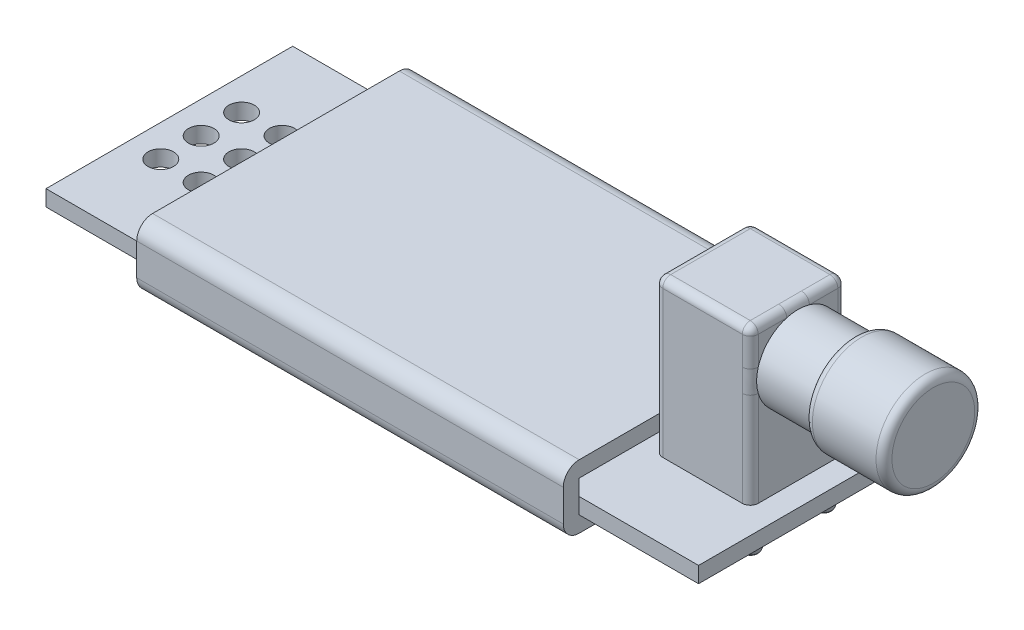
SolidWorks part; units mm, degrees
ref_plane "Спереди" through (0, 0, 0) normal (0, 0, 1) x (1, 0, 0)
ref_plane "Сверху" through (0, 0, 0) normal (0, 1, 0) x (1, 0, 0)
ref_plane "Справа" through (0, 0, 0) normal (1, 0, 0) x (0, 0, -1)
sketch "Эскиз1" plane through (0, 0, 0) normal (0, 1, 0) x (1, 0, 0)
  line L1 (-20.5, 7.75) -> (20.5, 7.75)
  line L2 (-20.5, 7.75) -> (-20.5, -7.75)
  line L3 (-20.5, -7.75) -> (20.5, -7.75)
  line L4 (20.5, 7.75) -> (20.5, -7.75)
  line L5 (-20.5, 7.75) -> (20.5, -7.75) construction
  line L6 (-20.5, -7.75) -> (20.5, 7.75) construction
  point P0 (0, 0)
  dimension "D1" = 15.5
  dimension "D2" = 41
extrude "Бобышка-Вытянуть1" add sketch "Эскиз1" along normal blind 1
sketch "Эскиз2" plane through (0, 1, 0) normal (0, 1, 0) x (1, 0, 0)
  line L1 (13, 3) -> (19, 3)
  line L2 (13, 3) -> (13, -3)
  line L3 (13, -3) -> (19, -3)
  line L4 (19, 3) -> (19, -3)
  line L5 (20.5, -7.75) -> (20.5, 7.75) construction
  point P4 (13, 0)
  dimension "D1" = 6
  dimension "D2" = 1.5
extrude "Бобышка-Вытянуть2" add sketch "Эскиз2" along normal blind 9.7
sketch "Эскиз3" plane through (19, 0, 0) normal (1, 0, 0) x (0, 0, -1)
  line L0 (-3, 10.7) -> (3, 10.7) construction
  line L1 (0, 10.7) -> (0, 7.7) construction
  line L2 (0, 7.7) -> (-3, 7.7) construction
  line L3 (-3, 10.7) -> (-3, 1) construction
  circle A0 centre (0, 7.7) radius 2.6
  point P5 (0, 10.7)
  dimension "D1" = 5.2
extrude "Бобышка-Вытянуть3" add sketch "Эскиз3" along normal blind 3.5
sketch "Эскиз4" plane through (0, 1, 0) normal (0, 1, 0) x (1, 0, 0)
  line L0 (-20.5, 7.75) -> (-20.5, -7.75) construction
  circle A0 centre (-18.5, -2.54) radius 0.8
  circle A1 centre (-15.96, -2.54) radius 0.8
  circle A2 centre (-15.96, 0) radius 0.8
  circle A3 centre (-15.96, 2.54) radius 0.8
  circle A4 centre (-18.5, 0) radius 0.8
  circle A5 centre (-18.5, 2.54) radius 0.8
  point P16 (-20.5, 0)
  dimension "D3" = 1.6
  dimension "D4" = 2.54
  dimension "D5" = 2
  dimension "D6" = 2.54
  dimension "D1" = 2
  dimension "D2" = 3
extrude "Вырез-Вытянуть1" cut sketch "Эскиз4" against normal through all contours A0 | A4 | A5 | A3 | A2 | A1 region at (-18.5, 1, 2.54) region at (-15.96, 1, 0) region at (-15.96, 1, -2.54) region at (-18.5, 1, 0) region at (-18.5, 1, -2.54)
sketch "Эскиз5" plane through (22.5, 0, 0) normal (1, 0, 0) x (0, 0, -1)
  circle A0 centre (0, 7.7) radius 3.1
  dimension "D1" = 6.2
extrude "Бобышка-Вытянуть4" add sketch "Эскиз5" along normal blind 5
fillet "Скругление1" radius 0.5 2 edges at (27.5, 7.7, -3.1) (22.5, 7.7, -3.1)
fillet "Скругление2" radius 0.5 8 edges at (19, 5.85, 3) (19, 10.7, 0) (16, 10.7, 3) (13, 5.85, 3) (13, 10.7, 0) (16, 10.7, -3) (19, 5.85, -3) (13, 5.85, -3)
sketch "Эскиз6" plane through (0, 0, 0) normal (0, -1, 0) x (1, 0, 0)
  line L0 (20.5, 7.75) -> (20.5, -7.75) construction
  line L1 (13.7, 2.3) -> (18.3, 2.3) construction
  line L2 (13.7, 2.3) -> (13.7, -2.3) construction
  line L3 (13.7, -2.3) -> (18.3, -2.3) construction
  line L4 (18.3, 2.3) -> (18.3, -2.3) construction
  line L5 (13.7, 2.3) -> (18.3, -2.3) construction
  line L6 (13.7, -2.3) -> (18.3, 2.3) construction
  circle A0 centre (13.7, 2.3) radius 1.2
  circle A1 centre (18.3, 2.3) radius 1.2
  circle A2 centre (18.3, -2.3) radius 1.2
  circle A3 centre (16, 0) radius 1.2
  circle A4 centre (13.7, -2.3) radius 1.2
  point P0 (16, 0)
  dimension "D4" = 2.4
  dimension "D1" = 4.6
  dimension "D2" = 4.6
  dimension "D3" = 2.2
extrude "Бобышка-Вытянуть5" add sketch "Эскиз6" along normal blind 2 draft 20
fillet "Скругление3" radius 0.2 5 edges at (13.7, -2, -2.7721) (18.3, -2, -2.7721) (16, -2, -0.4721) (18.3, -2, 1.8279) (13.7, -2, 1.8279)
sketch "Эскиз7" plane through (0, 1, 0) normal (0, 1, 0) x (1, 0, 0)
  line L0 (20.5, 7.75) -> (-20.5, 7.75) construction
  line L1 (-13.8, 6.75) -> (12, 6.75)
  line L2 (-13.8, 6.75) -> (-13.8, -6.05)
  line L3 (-13.8, -6.05) -> (12, -6.05)
  line L4 (12, 6.75) -> (12, -6.05)
  line L5 (-13.8, 6.75) -> (12, -6.05) construction
  line L6 (-13.8, -6.05) -> (12, 6.75) construction
  line L7 (-20.5, -7.75) -> (20.5, -7.75) construction
  line L8 (-20.5, 7.75) -> (-20.5, -7.75) construction
  line L9 (13, 2.5) -> (13, -2.5) construction
  point P0 (-0.9, 0.35)
  dimension "D1" = 1
  dimension "D2" = 1.7
  dimension "D3" = 6.7
  dimension "D4" = 1
extrude "Бобышка-Вытянуть6" add sketch "Эскиз7" along normal blind 1
fillet "Скругление4" radius 0.2 4 edges at (-0.9, 2, 6.05) (-13.8, 2, -0.35) (-0.9, 2, -6.75) (12, 2, -0.35)
sketch "Эскиз8" plane through (-13.8, 0, 0) normal (-1, 0, 0) x (0, 0, 1)
  line L0 (7.75, 1) -> (7.75, 0) construction
  line L1 (-7.75, 1) -> (-7.75, 0) construction
  line L2 (-7.75, 0) -> (7.75, 0) construction
  line L3 (-6.55, 2) -> (5.85, 2) construction
  line L4 (7.75, 2) -> (7.75, 0)
  line L5 (-7.75, 2) -> (-7.75, 0)
  line L6 (-7.75, 0) -> (7.75, 0)
  line L7 (-7.75, 2) -> (7.75, 2)
  line L8 (-7.75, 3) -> (7.75, 3)
  line L9 (8.75, 2) -> (8.75, 0)
  line L10 (-7.75, -1) -> (7.75, -1)
  line L11 (-8.75, 2) -> (-8.75, 0)
  line L12 (-8.75, 3) -> (8.75, 3) construction
  line L13 (8.75, 3) -> (8.75, -1) construction
  line L14 (-8.75, -1) -> (8.75, -1) construction
  line L15 (-8.75, 3) -> (-8.75, -1) construction
  arc A0 (7.75, 3) -> (8.75, 2) centre (7.75, 2) cw
  arc A1 (8.75, 0) -> (7.75, -1) centre (7.75, 0) cw
  arc A2 (-7.75, -1) -> (-8.75, 0) centre (-7.75, 0) cw
  arc A3 (-7.75, 3) -> (-8.75, 2) centre (-7.75, 2) ccw
  point P4 (7.75, 2)
  point P6 (-7.75, 2)
  point P8 (-7.6073, 2)
  point P11 (7.6416, 2)
  dimension "D2" = 1
  dimension "D1" = 1
extrude "Бобышка-Вытянуть7" add sketch "Эскиз8" against normal up to surface (26.8 mm away) separate body contours L8 A3 L11 A2 L10 A1 L9 A0 L5 L7 L4 L6 region at (-13.8, 2.8205, 0) up to face at (13, 5.6, 0)
